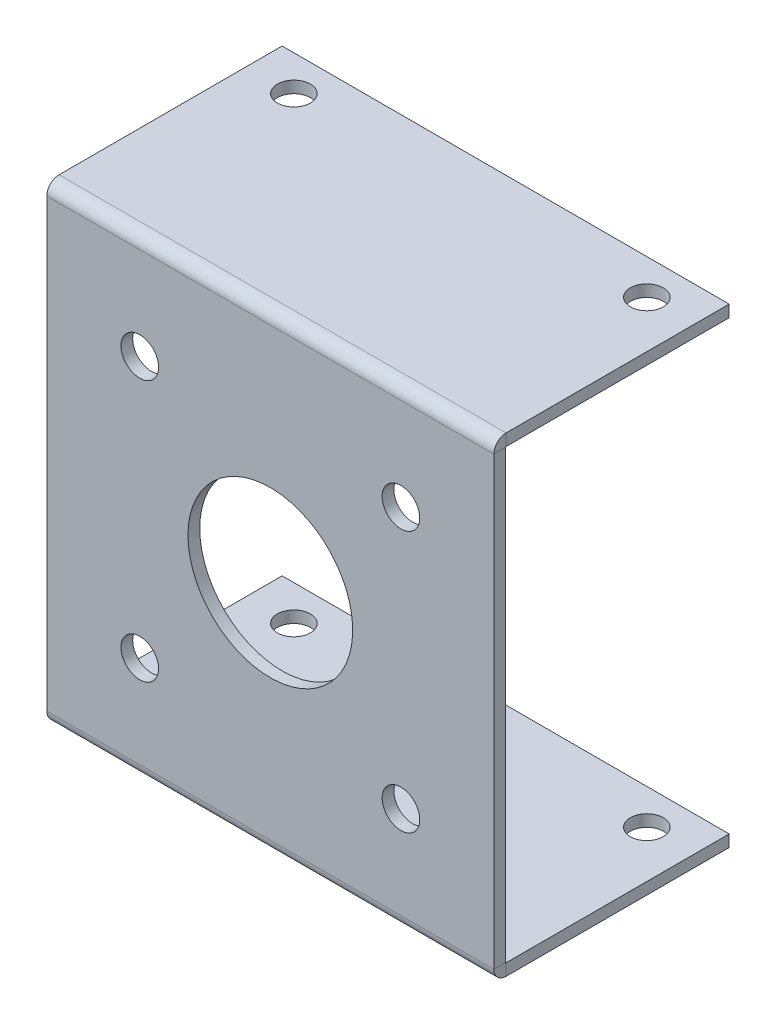
SolidWorks part; units mm, degrees
note: The reader was unsure of these and kept them because the rebuilt part matched: flange length of "Edge-Flange1", "Edge-Flange2".
material "ASTM A36 Steel"
ref_plane "Front Plane" through (0, 0, 0) normal (0, 0, 1) x (1, 0, 0)
ref_plane "Top Plane" through (0, 0, 0) normal (0, 1, 0) x (1, 0, 0)
ref_plane "Right Plane" through (0, 0, 0) normal (1, 0, 0) x (0, 0, -1)
sketch "Sketch1" plane through (0, 0, 0) normal (0, 0, 1) x (1, 0, 0)
  line L1 (-95, -100) -> (95, -100)
  line L2 (-95, -100) -> (-95, 100)
  line L3 (-95, 100) -> (95, 100)
  line L4 (95, -100) -> (95, 100)
  line L5 (-95, -100) -> (95, 100) construction
  line L6 (-95, 100) -> (95, -100) construction
  point P0 (0, 0)
  dimension "D1" = 190
  dimension "D2" = 200
base flange "Base-Flange1" sketch "Sketch1" thickness 5 reverse thickness direction no parameters "D1"=0.2
edge flange "Edge-Flange1" sketch "Sketch8" flange angle 90 flange length 100 flange position material inside bend radius 0.2 thickness 5 relief rectangular parameters "D6"=10
sketch "Sketch8" plane through (0, 100, -5) normal (0, -1, 0) x (-1, 0, 0)
  line L2 (-95, 0) -> (-95, 95)
  line L3 (-95, 95) -> (95, 95)
  line L4 (95, 95) -> (95, 0)
  line L9 (95, 0) -> (-95, 0) construction
  line L10 (95, 0) -> (-95, 0)
bend "EdgeBend1" bend radius 0.2 bend angle 90 parameters "D5"=1
edge flange "Edge-Flange2" sketch "Sketch11" flange angle 90 flange length 100 flange position material inside bend radius 0.2 thickness 5 relief rectangular parameters "D6"=10
sketch "Sketch11" plane through (0, -100, -5) normal (0, -1, 0) x (-1, 0, 0)
  line L2 (-95, 0) -> (-95, 95)
  line L3 (-95, 95) -> (95, 95)
  line L4 (95, 95) -> (95, 0)
  line L7 (95, 0) -> (-95, 0) construction
  line L8 (95, 0) -> (-95, 0)
bend "EdgeBend2" bend radius 0.2 bend angle 90 parameters "D5"=2
sketch "Sketch12" plane through (0, 0, 0) normal (0, 0, 1) x (1, 0, 0)
  circle A0 centre (0, 0) radius 35
  dimension "D1" = 70
extrude "Cut-Extrude1" cut sketch "Sketch12" against normal through all both and the other way through all normal cut yes
sketch "Sketch13" plane through (0, 0, 0) normal (0, 0, 1) x (1, 0, 0)
  circle A0 centre (55.5, 55.5) radius 8
  circle A1 centre (-55.5, 55.5) radius 8
  circle A2 centre (-55.5, -55.5) radius 8
  circle A3 centre (55.5, -55.5) radius 8
  point P0 (0, 0)
  dimension "D3" = 16
  dimension "D4" = 16
  dimension "D5" = 16
  dimension "D6" = 16
  dimension "D1" = 111
  dimension "D2" = 111
extrude "Cut-Extrude2" cut sketch "Sketch13" against normal through all both and the other way through all normal cut yes
sketch "Sketch14" plane through (0, -100, 0) normal (0, -1, 0) x (-1, 0, 0)
  line L0 (-95, 100) -> (-95, 5.2) construction
  line L1 (95, 5.2) -> (95, 100) construction
  line L2 (95, 100) -> (-95, 100) construction
  circle A0 centre (75, 85) radius 7
  circle A1 centre (-75, 85) radius 7
  dimension "D1" = 14
  dimension "D2" = 14
  dimension "D3" = 20
  dimension "D4" = 20
  dimension "D5" = 15
  dimension "D6" = 15
extrude "Cut-Extrude3" cut sketch "Sketch14" against normal through all both and the other way through all normal cut yes
sketch "Bend-Lines1" [suppressed] plane through (0, 0, 0) normal (0, 1, 0) x (1, 0, 0)
sketch "Bounding-Box1" [suppressed] plane through (0, 0, 0) normal (0, 1, 0) x (1, 0, 0)
sheet metal parameters "Sheet-Metal1" thickness 5 parameters "D1"=0.2
flat pattern "Flat-Pattern1" [suppressed]
sketch "Bend-Lines2" plane through (0, 0, 0) normal (0, 1, 0) x (1, 0, 0)
sketch3d "Bounding-Box2" [suppressed]
  line L0 (-85, 100, 0) -> (-85, -100, 0) construction
  line L1 (85, 100, 0) -> (85, -100, 0) construction
  line L2 (-85, 100, 0) -> (85, 100, 0) construction
  line L3 (-85, -100, 0) -> (85, -100, 0) construction
sheet metal parameters "Sheet-Metal2" thickness 5 parameters "D1"=0.2
flat pattern "Flat-Pattern1"
sketch "Bend-Lines2" plane through (0, 0, 0) normal (0, 0, 1) x (1, 0, 0)
  line L0 (85, 96.9206) -> (-85, 96.9206) construction
  line L1 (85, 96.9206) -> (-85, 96.9206) construction
sketch3d "Bounding-Box2" [suppressed]
  line L0 (85, 143.8412, 0) -> (85, -100, 0) construction
  line L1 (-85, 143.8412, 0) -> (-85, -100, 0) construction
  line L2 (85, 143.8412, 0) -> (-85, 143.8412, 0) construction
  line L3 (85, -100, 0) -> (-85, -100, 0) construction
bend of the flat pattern "Flatten-<EdgeBend1>1"
sheet metal parameters "Sheet-Metal3" thickness 5 parameters "D1"=0.2
flat pattern "Flat-Pattern1"
sketch "Bend-Lines2" plane through (0, 0, 0) normal (0, 0, 1) x (1, 0, 0)
  line L0 (85, 96.9206) -> (-85, 96.9206) construction
  line L1 (85, 96.9206) -> (-85, 96.9206) construction
  line L2 (-85, -96.9206) -> (85, -96.9206) construction
  line L3 (-85, -96.9206) -> (85, -96.9206) construction
sketch3d "Bounding-Box2" [suppressed]
  line L0 (85, 143.8412, 0) -> (85, -143.8412, 0) construction
  line L1 (-85, 143.8412, 0) -> (-85, -143.8412, 0) construction
  line L2 (85, 143.8412, 0) -> (-85, 143.8412, 0) construction
  line L3 (85, -143.8412, 0) -> (-85, -143.8412, 0) construction
bend of the flat pattern "Flatten-<EdgeBend1>1"
bend of the flat pattern "Flatten-<EdgeBend2>1"
sheet metal parameters "Sheet-Metal4" thickness 5 parameters "D1"=0.2
flat pattern "Flat-Pattern1"
sketch "Bend-Lines2" plane through (0, 0, 0) normal (0, 0, 1) x (1, 0, 0)
  line L0 (85, 96.9206) -> (-85, 96.9206) construction
  line L1 (85, 96.9206) -> (-85, 96.9206) construction
  line L2 (-85, -96.9206) -> (85, -96.9206) construction
  line L3 (-85, -96.9206) -> (85, -96.9206) construction
sketch3d "Bounding-Box2" [suppressed]
  line L0 (85, 143.8412, 0) -> (85, -143.8412, 0) construction
  line L1 (-85, 143.8412, 0) -> (-85, -143.8412, 0) construction
  line L2 (85, 143.8412, 0) -> (-85, 143.8412, 0) construction
  line L3 (85, -143.8412, 0) -> (-85, -143.8412, 0) construction
bend of the flat pattern "Flatten-<EdgeBend1>1"
bend of the flat pattern "Flatten-<EdgeBend2>1"
sheet metal parameters "Sheet-Metal5" thickness 5 parameters "D1"=0.2
flat pattern "Flat-Pattern1"
sketch "Bend-Lines2" plane through (0, 0, 0) normal (0, 0, 1) x (1, 0, 0)
  line L0 (85, 96.9206) -> (-85, 96.9206) construction
  line L1 (85, 96.9206) -> (-85, 96.9206) construction
  line L2 (-85, -96.9206) -> (85, -96.9206) construction
  line L3 (-85, -96.9206) -> (85, -96.9206) construction
sketch3d "Bounding-Box2" [suppressed]
  line L0 (85, 143.8412, 0) -> (85, -143.8412, 0) construction
  line L1 (-85, 143.8412, 0) -> (-85, -143.8412, 0) construction
  line L2 (85, 143.8412, 0) -> (-85, 143.8412, 0) construction
  line L3 (85, -143.8412, 0) -> (-85, -143.8412, 0) construction
bend of the flat pattern "Flatten-<EdgeBend1>1"
bend of the flat pattern "Flatten-<EdgeBend2>1"
sheet metal parameters "Sheet-Metal6" thickness 5 parameters "D1"=0.2
flat pattern "Flat-Pattern1"
sketch "Bend-Lines2" plane through (0, 0, 0) normal (0, 0, 1) x (1, 0, 0)
  line L0 (95, 96.9206) -> (-95, 96.9206) construction
  line L1 (95, 96.9206) -> (-95, 96.9206) construction
  line L2 (-95, -96.9206) -> (95, -96.9206) construction
  line L3 (-95, -96.9206) -> (95, -96.9206) construction
sketch3d "Bounding-Box2" [suppressed]
  line L0 (95, 193.8412, 0) -> (95, -193.8412, 0) construction
  line L1 (-95, 193.8412, 0) -> (-95, -193.8412, 0) construction
  line L2 (95, 193.8412, 0) -> (-95, 193.8412, 0) construction
  line L3 (95, -193.8412, 0) -> (-95, -193.8412, 0) construction
bend of the flat pattern "Flatten-<EdgeBend1>1"
bend of the flat pattern "Flatten-<EdgeBend2>1"
